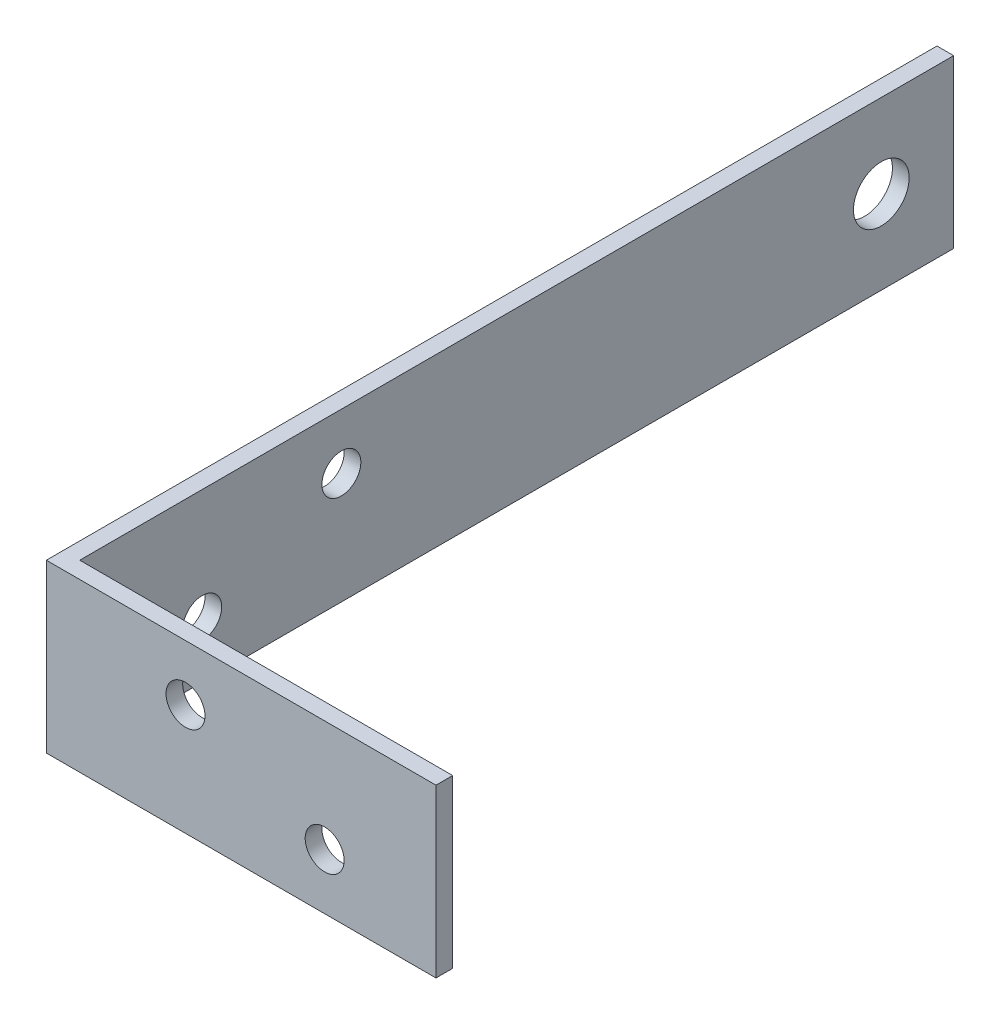
SolidWorks part; units mm, degrees
ref_plane "Спереди" through (0, 0, 0) normal (0, 0, 1) x (1, 0, 0)
ref_plane "Сверху" through (0, 0, 0) normal (0, 1, 0) x (1, 0, 0)
ref_plane "Справа" through (0, 0, 0) normal (1, 0, 0) x (0, 0, -1)
sketch "Эскиз1" plane through (0, 0, 0) normal (0, 1, 0) x (1, 0, 0)
  line L0 (0, 0) -> (70, 0)
  line L1 (0, 0) -> (0, 120)
  line L2 (0, 120) -> (0, 160)
extrude "Вытянуть-Тонкостенный1" add sketch "Эскиз1" along normal blind 30 thin thin type one direction wall 3
sketch "Эскиз2" plane through (0, 0, 0) normal (-1, 0, 0) x (0, 0, 1)
  circle A1 centre (-50, 20) radius 3.5
  circle A2 centre (-25, 10) radius 3.5
extrude "Вырез-Вытянуть1" cut sketch "Эскиз2" against normal through all
sketch "Эскиз3" plane through (0, 0, 0) normal (0, 0, 1) x (1, 0, 0)
  circle A0 centre (25, 20) radius 3.5
  circle A1 centre (50, 10) radius 3.5
extrude "Вырез-Вытянуть2" cut sketch "Эскиз3" against normal through all
sketch "Эскиз4" plane through (0, 0, 0) normal (-1, 0, 0) x (0, 0, 1)
  circle A0 centre (-147, 15) radius 5
extrude "Вырез-Вытянуть3" cut sketch "Эскиз4" against normal through all
